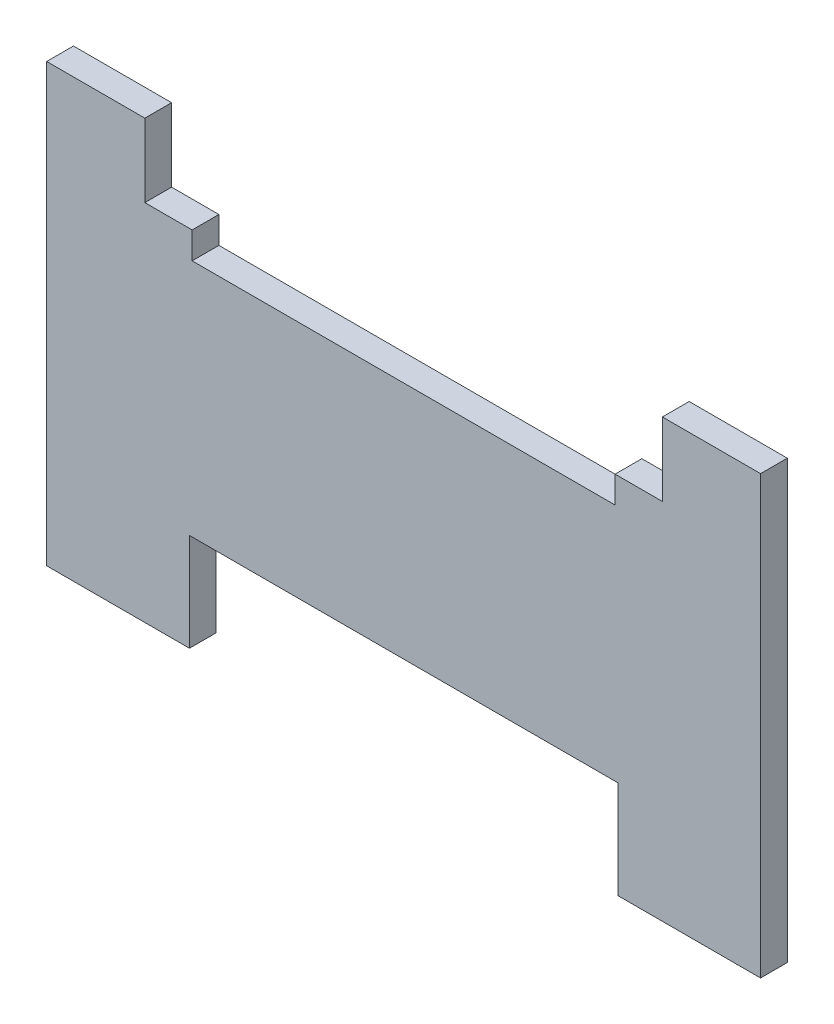
SolidWorks part; units mm, degrees
ref_plane "Front Plane" through (0, 0, 0) normal (0, 0, 1) x (1, 0, 0)
ref_plane "Top Plane" through (0, 0, 0) normal (0, 1, 0) x (1, 0, 0)
ref_plane "Right Plane" through (0, 0, 0) normal (1, 0, 0) x (0, 0, -1)
sketch "Sketch1" plane through (0, 0, 0) normal (0, 0, 1) x (1, 0, 0)
  line L0 (0, 52.125) -> (11, 52.125)
  line L1 (80, 52.125) -> (80, 3.175)
  line L2 (80, 3.175) -> (64, 3.175)
  line L3 (64, 3.175) -> (64, 14.125)
  line L4 (64, 14.125) -> (16, 14.125)
  line L5 (16, 14.125) -> (16, 3.175)
  line L6 (16, 3.175) -> (0, 3.175)
  line L7 (0, 3.175) -> (0, 52.125)
  line L8 (16, 3.175) -> (0, 3.175) construction
  line L9 (0, 14.125) -> (80, 14.125) construction
  line L10 (16, 17.125) -> (16, 3.175) construction
  line L11 (64, 17.125) -> (64, 3.175) construction
  line L12 (80, 3.175) -> (80, 52.125) construction
  line L13 (0, 3.175) -> (0, 52.125) construction
  line L15 (40, 14.125) -> (40, 52.125) construction
  line L16 (40, 0) -> (40, 67.125) construction
  line L17 (3, 49.125) -> (3, 6.175) construction
  line L18 (3, 6.175) -> (16, 6.175) construction
  line L19 (64, 6.175) -> (77, 6.175) construction
  line L20 (77, 6.175) -> (77, 49.125) construction
  line L21 (77, 49.125) -> (3, 49.125) construction
  line L22 (0, 17.125) -> (80, 17.125) construction
  line L23 (64, 14.125) -> (80, 14.125) construction
  line L24 (16, 14.125) -> (0, 14.125) construction
  line L25 (8, 3.175) -> (8, 6.175) construction
  line L26 (72, 3.175) -> (72, 6.175) construction
  line L27 (77, 6.175) -> (77, 49.125) construction
  line L28 (77, 6.175) -> (64, 6.175) construction
  line L29 (72, 3.175) -> (72, 6.175) construction
  line L30 (16, 6.175) -> (3, 6.175) construction
  line L31 (3, 6.175) -> (3, 49.125) construction
  line L32 (8, 3.175) -> (8, 6.175) construction
  line L33 (80, 17.125) -> (0, 17.125) construction
  line L34 (77, 49.125) -> (3, 49.125) construction
  line L35 (46.8, 50.175) -> (46.8, 8.175) construction
  line L36 (46.8, 8.175) -> (43.8, 8.175) construction
  line L37 (43.8, 50.175) -> (43.8, 8.175) construction
  line L38 (46.8, 50.175) -> (43.8, 50.175) construction
  line L39 (46.8, 50.175) -> (46.8, 8.175) construction
  line L40 (46.8, 8.175) -> (43.8, 8.175) construction
  line L41 (43.8, 50.175) -> (43.8, 8.175) construction
  line L42 (46.8, 50.175) -> (43.8, 50.175) construction
  line L43 (72, 40.925) -> (72, 52.125) construction
  line L44 (0, 52.125) -> (80, 52.125) construction
  line L45 (8, 52.125) -> (8, 40.925) construction
  line L46 (8, 40.925) -> (72, 40.925) construction
  line L47 (72, 52.125) -> (72, 40.925) construction
  line L48 (8, 40.925) -> (8, 52.125) construction
  line L49 (16.3, 40.925) -> (8, 40.925) construction
  line L50 (8, 52.125) -> (16.3, 52.125) construction
  line L51 (11, 49.125) -> (11, 43.925) construction
  line L53 (11, 52.125) -> (11, 43.925)
  line L54 (11, 43.925) -> (69, 43.925) construction
  line L55 (69, 52.125) -> (69, 43.925)
  line L56 (69, 52.125) -> (80, 52.125)
  line L57 (69, 49.125) -> (69, 43.925) construction
  line L59 (69, 43.925) -> (63.7, 43.925) construction
  line L60 (16.3, 52.125) -> (16.3, 49.125) construction
  line L61 (16.3, 43.925) -> (16.3, 40.925)
  line L62 (16.3, 52.125) -> (16.3, 49.125) construction
  line L63 (63.7, 52.125) -> (63.7, 49.125) construction
  line L64 (63.7, 43.925) -> (63.7, 40.925)
  line L65 (63.7, 52.125) -> (63.7, 49.125) construction
  line L66 (49.8, 53.175) -> (49.8, 5.175) construction
  line L67 (49.8, 5.175) -> (40.8, 5.175) construction
  line L70 (40.8, 53.175) -> (40.8, 5.175) construction
  line L71 (49.8, 53.175) -> (40.8, 53.175) construction
  line L72 (63.7, 43.925) -> (69, 43.925)
  line L73 (11, 43.925) -> (16.3, 43.925)
  line L74 (40.8, 53.175) -> (40.8, 44.225) construction
  line L80 (16.3, 40.925) -> (63.7, 40.925)
sketch "Sketch2" plane through (0, 0, 0) normal (1, 0, 0) x (0, 0, -1)
  line L1 (0, 52.125) -> (3, 52.125)
  line L2 (0, 52.125) -> (0, 3.175)
  line L3 (0, 3.175) -> (3, 3.175)
  line L4 (3, 52.125) -> (3, 3.175)
extrude "Boss-Extrude1" add sketch "Sketch1" against normal up to vertex (3 mm away) up to point (0, 52.125, -3)
